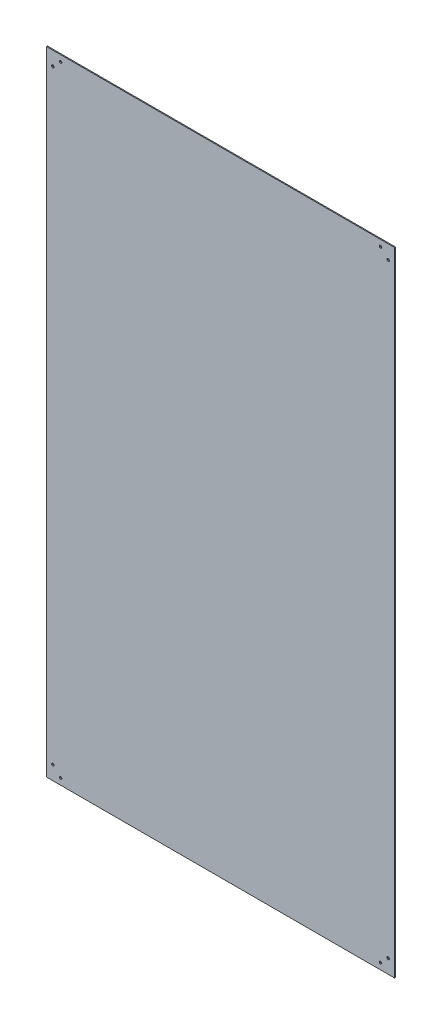
SolidWorks part; units mm, degrees
ref_plane "Piano frontale" through (0, 0, 0) normal (0, 0, 1) x (1, 0, 0)
ref_plane "Piano superiore" through (0, 0, 0) normal (0, 1, 0) x (1, 0, 0)
ref_plane "Piano destro" through (0, 0, 0) normal (1, 0, 0) x (0, 0, -1)
sketch "Schizzo1" plane through (0, 0, 0) normal (0, 0, 1) x (1, 0, 0)
  line L1 (-550, 1000) -> (550, 1000)
  line L2 (-550, 1000) -> (-550, -1000)
  line L3 (-550, -1000) -> (550, -1000)
  line L4 (550, 1000) -> (550, -1000)
  line L5 (-550, 1000) -> (550, -1000) construction
  line L6 (-550, -1000) -> (550, 1000) construction
  point P0 (0, 0)
  dimension "D1" = 2000
  dimension "D2" = 1100
base flange "Base-Flangia1" sketch "Schizzo1" thickness 3 reverse thickness direction no parameters "D1"=1
sketch "Schizzo2" plane through (0, 0, 0) normal (0, 0, 1) x (1, 0, 0)
  line L0 (0, -1000) -> (0, 49000) construction
  line L1 (-1000, 0) -> (49000, 0) construction
  line L2 (-550, 1000) -> (-550, -1000) construction
  line L3 (-550, -1000) -> (550, -1000) construction
  circle A0 centre (-530, -955.75) radius 4
  circle A1 centre (530, -955.75) radius 4
  circle A2 centre (-530, 955.75) radius 4
  circle A3 centre (530, 955.75) radius 4
  circle A4 centre (-505.75, -980) radius 4
  circle A5 centre (505.75, -980) radius 4
  circle A6 centre (505.75, 980) radius 4
  circle A7 centre (-505.75, 980) radius 4
  dimension "D1" = 8
  dimension "D6" = 8
  dimension "D2" = 20
  dimension "D3" = 44.25
  dimension "D4" = 44.25
  dimension "D5" = 20
extrude "Taglio-Estrusione1" cut sketch "Schizzo2" against normal through all normal cut yes
sketch "Linee di piegatura1" [suppressed] plane through (0, 0, 0) normal (0, 1, 0) x (1, 0, 0)
sketch "Casella di contorno1" [suppressed] plane through (0, 0, 0) normal (0, 1, 0) x (1, 0, 0)
sheet metal parameters "Lamiera1" thickness 3 parameters "D1"=1
flat pattern "Ripetizione piatta1" [suppressed]
sketch "Linee di piegatura2" plane through (0, 0, 0) normal (0, 1, 0) x (1, 0, 0)
sketch3d "Casella di contorno2" [suppressed]
  line L0 (550, 1000, 0) -> (550, -1000, 0) construction
  line L1 (-550, 1000, 0) -> (-550, -1000, 0) construction
  line L2 (550, 1000, 0) -> (-550, 1000, 0) construction
  line L3 (550, -1000, 0) -> (-550, -1000, 0) construction
sheet metal parameters "Lamiera3" thickness 3 parameters "D1"=1
flat pattern "Ripetizione piatta1"
sketch "Linee di piegatura2" plane through (0, 0, 0) normal (0, 1, 0) x (1, 0, 0)
sketch3d "Casella di contorno2" [suppressed]
  line L0 (550, 1000, 0) -> (550, -1000, 0) construction
  line L1 (-550, 1000, 0) -> (-550, -1000, 0) construction
  line L2 (550, 1000, 0) -> (-550, 1000, 0) construction
  line L3 (550, -1000, 0) -> (-550, -1000, 0) construction
